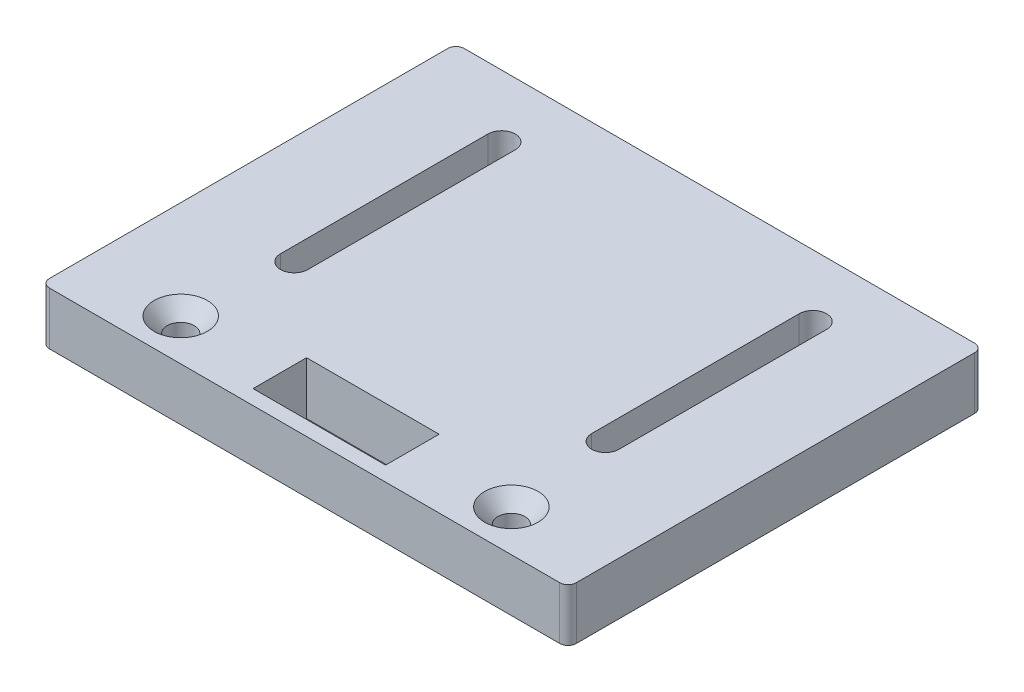
SolidWorks part; units mm, degrees
ref_plane "前基準面" through (0, 0, 0) normal (0, 0, 1) x (1, 0, 0)
ref_plane "上基準面" through (0, 0, 0) normal (0, 1, 0) x (1, 0, 0)
ref_plane "右基準面" through (0, 0, 0) normal (1, 0, 0) x (0, 0, -1)
sketch "Sketch1" plane through (0, 0, 0) normal (0, 1, 0) x (1, 0, 0)
  line L1 (0, 0) -> (127, 0)
  line L2 (0, 0) -> (0, 100)
  line L3 (0, 100) -> (127, 100)
  line L4 (127, 0) -> (127, 100)
extrude "Boss-Extrude1" add sketch "Sketch1" along normal blind 12.7
sketch "Sketch2" plane through (0, 12.7, 0) normal (0, 1, 0) x (1, 0, 0)
  line L6 (47.53, 10) -> (47.53, 16.45)
  line L7 (47.53, 16.45) -> (79.48, 16.45)
  line L8 (79.48, 10) -> (79.48, 16.45)
  line L9 (47.53, 10) -> (47.53, 3.55)
  line L10 (47.53, 3.55) -> (79.48, 3.55)
  line L11 (79.48, 3.55) -> (79.48, 10)
  dimension "D1" = 31.95
  dimension "D2" = 12.9
extrude "Cut-Extrude1" cut sketch "Sketch2" against normal blind 12.7
sketch "Sketch4" plane through (0, 12.7, 0) normal (0, 1, 0) x (1, 0, 0)
  point P7 (23.65, 9.9969)
  point P8 (103.35, 9.9969)
sketch "Sketch6" plane through (0, 12.7, 0) normal (0, 1, 0) x (1, 0, 0)
  line L1 (22.6908, 35) -> (22.6908, 85)
  line L2 (29.2908, 35) -> (29.2908, 85)
  line L10 (29.2908, 60) -> (97.7208, 60) construction
  line L13 (97.7208, 35) -> (97.7208, 85)
  line L14 (104.3091, 35.2777) -> (104.3091, 85.2777)
  line L15 (127, 100) -> (0, 100) construction
  line L16 (22.6908, 60) -> (0, 60.0215) construction
  line L17 (104.3091, 60.2777) -> (127, 60.2777) construction
  line L18 (127, 0) -> (127, 100) construction
  line L19 (0, 100) -> (0, 0) construction
  arc A6 (22.6908, 35) -> (29.2908, 35) centre (25.9908, 35) ccw
  arc A11 (29.2908, 85) -> (22.6908, 85) centre (25.9908, 85) ccw
  arc A12 (97.7208, 85) -> (104.3091, 85.2777) centre (101.0208, 85) cw
  arc A13 (104.3091, 35.2777) -> (97.7208, 35) centre (101.0208, 35) cw
  point P18 (127, 59.9917)
  point P23 (0, 60)
  point P26 (63.5058, 60)
  dimension "D1" = 50
  dimension "D2" = 3.3
  dimension "D4" = 3.3
  dimension "D6" = 15
  dimension "D7" = 22.6908
  dimension "D8" = 22.6909
  dimension "D9" = 15
  dimension "D3" = 68.43
  dimension "D5" = 50
extrude "Cut-Extrude2" cut sketch "Sketch6" against normal through all
fillet "Fillet1" radius 2 4 edges at (127, 6.35, -100) (127, 6.35, 0) (0, 6.35, 0) (0, 6.35, -100)
hole_wizard "CSK for 1/4 Flat Head Machine Screw1" positions "3DSketch1" profile "Sketch7" countersink size "1/4" standard "ANSI Inch" end condition through all
sketch3d "3DSketch1"
  point P0 (23.65, 12.7, -9.9969)
  point P3 (103.35, 12.7, -9.9969)
sketch "Sketch7" plane through (23.65, 12.7, -9.9969) normal (1, 0, 0) x (0, 0, 1)
  line L0 (0, 0) -> (0, 12.7)
  line L1 (0, 12.7) -> (3.2639, 12.7)
  line L2 (3.2639, 12.7) -> (3.2639, 3.6524)
  line L3 (3.2639, 3.6524) -> (6.4389, 0)
  line L5 (6.4389, 0) -> (0, 0)
  line L6 (-3.2639, 3.6524) -> (-6.4389, 0) construction
  line L11 (0, -6.35) -> (0, 107.95) construction
  dimension "Thru Hole Dia." = 6.5278
  dimension "Thru Hole Depth" = 12.7
  dimension "Near C'Sink Dia." = 12.8778
  dimension "Near C'Sink Angle" = 82
sketch "Sketch8" plane through (0, 12.7, 0) normal (0, 1, 0) x (1, 0, 0)
  point P4 (63.505, 10)
